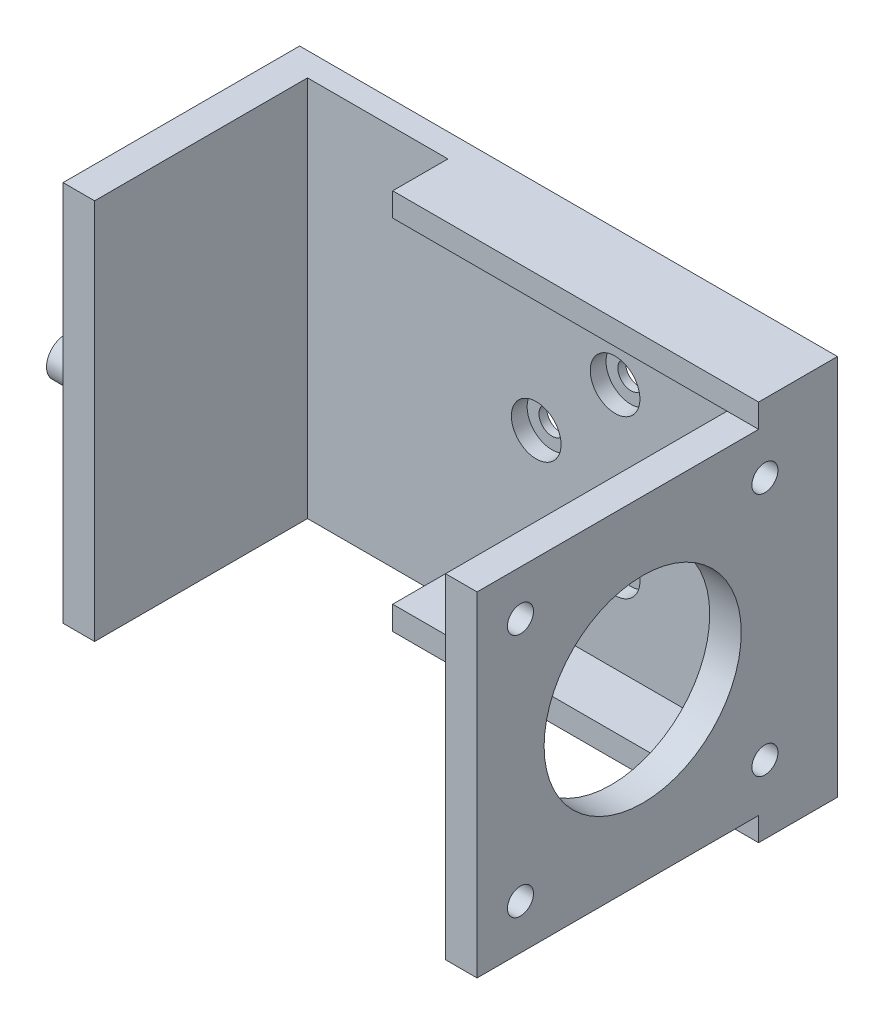
SolidWorks part; units mm, degrees
ref_plane "前视基准面" through (0, 0, 0) normal (0, 0, 1) x (1, 0, 0)
ref_plane "上视基准面" through (0, 0, 0) normal (0, 1, 0) x (1, 0, 0)
ref_plane "右视基准面" through (0, 0, 0) normal (1, 0, 0) x (0, 0, -1)
other "Configuration Table"
sketch "草图1" plane through (0, 0, 0) normal (0, 0, 1) x (1, 0, 0)
  line L1 (21.2, -21.2) -> (-21.2, -21.2)
  line L2 (21.2, -21.2) -> (21.2, 21.2)
  line L3 (21.2, 21.2) -> (-21.2, 21.2)
  line L4 (-21.2, -21.2) -> (-21.2, 21.2)
  line L5 (21.2, -21.2) -> (-21.2, 21.2) construction
  line L6 (21.2, 21.2) -> (-21.2, -21.2) construction
  circle A1 centre (0, 10) radius 1.65
  circle A2 centre (10, 0) radius 1.65
  circle A3 centre (0, -10) radius 1.65
  circle A4 centre (-10, 0) radius 1.65
  circle A5 centre (0, 10) radius 3.15
  circle A6 centre (10, 0) radius 3.15
  circle A7 centre (0, -10) radius 3.15
  circle A8 centre (-10, 0) radius 3.15
  point P14 (0, 0)
  point P18 (0, 0)
  dimension "D1" = 1.5
  dimension "D2" = 3.3
  dimension "D3" = 42.4
  dimension "D5" = 42.4
  dimension "D6" = 10
  dimension "D4" = 4
extrude "凸台-拉伸1" add sketch "草图1" along normal blind 3 contours L4 L1 L2 L3 A8 A7 A6 A5 region at (0, 0, 0)
extrude "凸台-拉伸2" add sketch "草图1<3>" along normal blind 1 contours A8 A4 | A5 A1 | A6 A2 | A7 A3 region at (-3.0609, 10, 0) region at (6.9391, 0, 0) region at (-3.0609, -10, 0) region at (-13.0609, 0, 0)
sketch "草图1<3>" plane through (0, 0, 0) normal (0, 0, 1) x (1, 0, 0) same geometry as "草图1"
sketch "草图2" plane through (0, 0, 0) normal (0, 0, 1) x (1, 0, 0)
  line L0 (21.2, -21.2) -> (-21.2, -21.2) construction
  line L1 (21.2, 21.2) -> (25.2, 21.2)
  line L2 (21.2, 21.2) -> (21.2, -21.2)
  line L3 (21.2, -21.2) -> (25.2, -21.2)
  line L4 (25.2, 21.2) -> (25.2, -21.2)
  dimension "D1" = 4
extrude "凸台-拉伸3" add sketch "草图2" along normal blind 45.7
sketch "草图3" plane through (0, 0, 0) normal (1, 0, 0) x (0, 0, -1)
  line L0 (-23.681, 0) -> (12.185, 0) construction
  line L1 (0, -21.2) -> (-3.7, -21.2) construction
  line L2 (0, -21.2) -> (0, 21.2) construction
  line L3 (0, 21.2) -> (-3.7, 21.2) construction
  line L4 (-3.7, -21.2) -> (-3.7, 21.2) construction
  line L5 (-24.7, -0.1) -> (-24.7, -37.8905) construction
  line L6 (-45.7, -21.2) -> (-45.7, 21.2) construction
  circle A0 centre (-9.2, -15.5) radius 1.65
  circle A1 centre (-40.2, -15.5) radius 1.65
  circle A2 centre (-40.2, 15.5) radius 1.65
  circle A3 centre (-9.2, 15.5) radius 1.65
  circle A4 centre (-24.7, 0) radius 12.5
  point P15 (-24.7, 0)
  point P25 (-24.7, 0)
  dimension "D1" = 3.3
  dimension "D6" = 25
  dimension "D2" = 15.5
  dimension "D3" = 21
  dimension "D4" = 15.5
  dimension "D7" = 3.7
  dimension "D5" = 4
extrude "切除-拉伸2" cut sketch "草图3" along normal blind 45.2
sketch "草图4" plane through (0, 0, 0) normal (0, 0, 1) x (1, 0, 0)
  line L0 (-21.2, -21.2) -> (-21.2, 21.2) construction
  line L1 (25.2, -21.2) -> (-21.2, -21.2)
  line L2 (25.2, -21.2) -> (25.2, -24.2)
  line L3 (25.2, -24.2) -> (-21.2, -24.2)
  line L4 (-21.2, -21.2) -> (-21.2, -24.2)
  line L5 (25.2, 21.2) -> (-21.2, 21.2)
  line L6 (25.2, 21.2) -> (25.2, 24.2)
  line L7 (25.2, 24.2) -> (-21.2, 24.2)
  line L8 (-21.2, 21.2) -> (-21.2, 24.2)
  dimension "D1" = 3
  dimension "D2" = 3
extrude "凸台-拉伸4" add sketch "草图4" along normal blind 10
sketch "草图9" plane through (0, 0, 0) normal (0, 0, 1) x (1, 0, 0)
  line L0 (25.2, -21.2) -> (25.2, 21.2) construction
  line L1 (-21.2, -24.2) -> (-39, -24.2)
  line L2 (-21.2, -24.2) -> (-21.2, 24.2)
  line L3 (-21.2, 24.2) -> (-39, 24.2)
  line L4 (-39, -24.2) -> (-39, 24.2)
  dimension "D1" = 64.2
extrude "凸台-拉伸8" add sketch "草图9" along normal blind 3
sketch "草图10" plane through (0, 0, 0) normal (0, 0, 1) x (1, 0, 0)
  line L0 (-21.2, 24.2) -> (-39, 24.2) construction
  line L1 (-39, -24.2) -> (-43, -24.2)
  line L2 (-39, -24.2) -> (-39, 24.2)
  line L3 (-39, 24.2) -> (-43, 24.2)
  line L4 (-43, -24.2) -> (-43, 24.2)
  dimension "D1" = 4
extrude "凸台-拉伸9" add sketch "草图10" along normal blind 30
sketch "草图11" plane through (0, 0, 0) normal (1, 0, 0) x (0, 0, -1)
  circle A1 centre (-24.7, 0) radius 2.4
  dimension "D1" = 4.8
extrude "凸台-拉伸10" add sketch "草图11" against normal blind 5 from surface starting at face at (-43, 0, 15)
